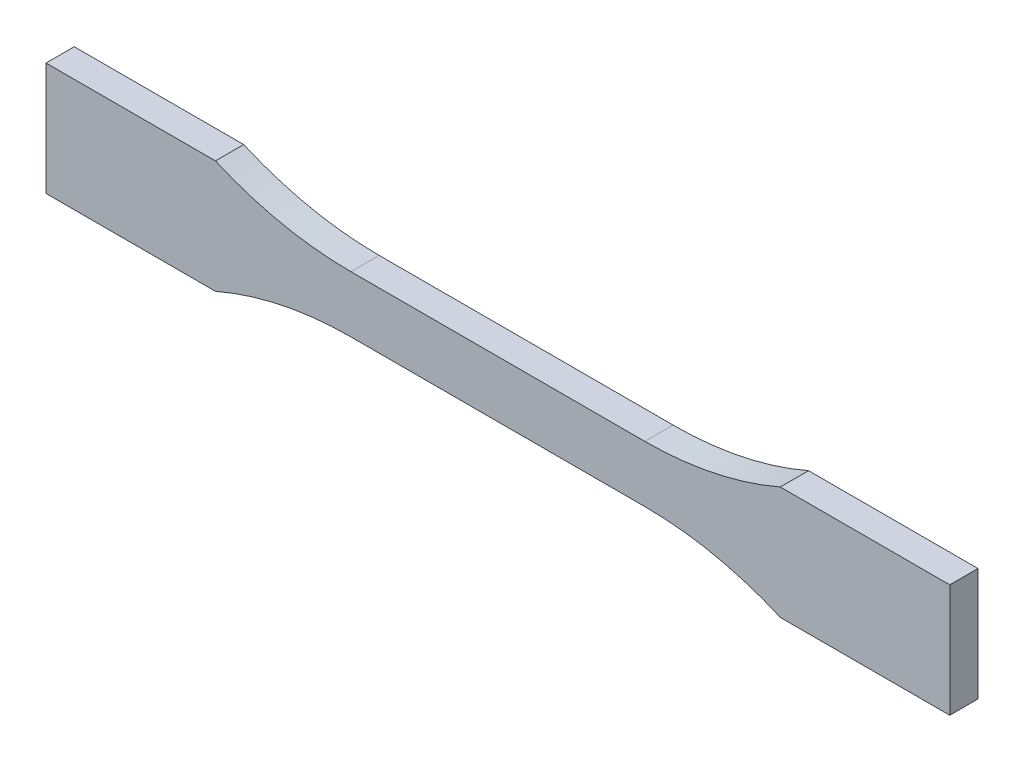
SolidWorks part; units mm, degrees
material "Custom Plastic"
ref_plane "Front Plane" through (0, 0, 0) normal (0, 0, 1) x (1, 0, 0)
ref_plane "Top Plane" through (0, 0, 0) normal (0, 1, 0) x (1, 0, 0)
ref_plane "Right Plane" through (0, 0, 0) normal (1, 0, 0) x (0, 0, -1)
sketch "Sketch1" plane through (0, 0, 0) normal (0, 0, 1) x (1, 0, 0)
  line L0 (0, -6.35) -> (0, 6.35) construction
  line L1 (-63.5, 6.35) -> (63.5, 6.35)
  line L2 (-63.5, -6.35) -> (63.5, -6.35)
  line L3 (-63.5, 6.35) -> (-63.5, -6.35) construction
  line L4 (-63.5, 6.35) -> (-63.5, -6.35) construction
  line L5 (-63.5, 12.7) -> (-101.6, 12.7)
  line L6 (-101.6, 12.7) -> (-101.6, -12.7)
  line L7 (-101.6, -12.7) -> (-63.5, -12.7)
  line L9 (-63.5, 0) -> (-101.6, 0) construction
  line L10 (63.5, 6.35) -> (63.5, -6.35) construction
  line L11 (63.5, -12.7) -> (63.5, -6.35)
  line L12 (63.5, 6.35) -> (63.5, 12.7)
  line L13 (63.5, 0) -> (101.6, 0) construction
  line L14 (101.6, -12.7) -> (63.5, -12.7)
  line L15 (101.6, 12.7) -> (101.6, -12.7)
  line L16 (63.5, 12.7) -> (101.6, 12.7)
  line L18 (-63.5, 12.7) -> (-63.5, 6.35)
  line L19 (-63.5, -6.35) -> (-63.5, -12.7)
  dimension "D1" = 203.2
  dimension "D2" = 25.4
  dimension "D3" = 12.7
  dimension "D4" = 127
extrude "1/4 Inch Thickness" add sketch "Sketch1" along normal mid plane 6.35
fillet "Fillet1" radius 76.2 4 edges at (63.5, -6.35, 0) (63.5, 6.35, 0) (-63.5, -6.35, 0) (-63.5, 6.35, 0)
